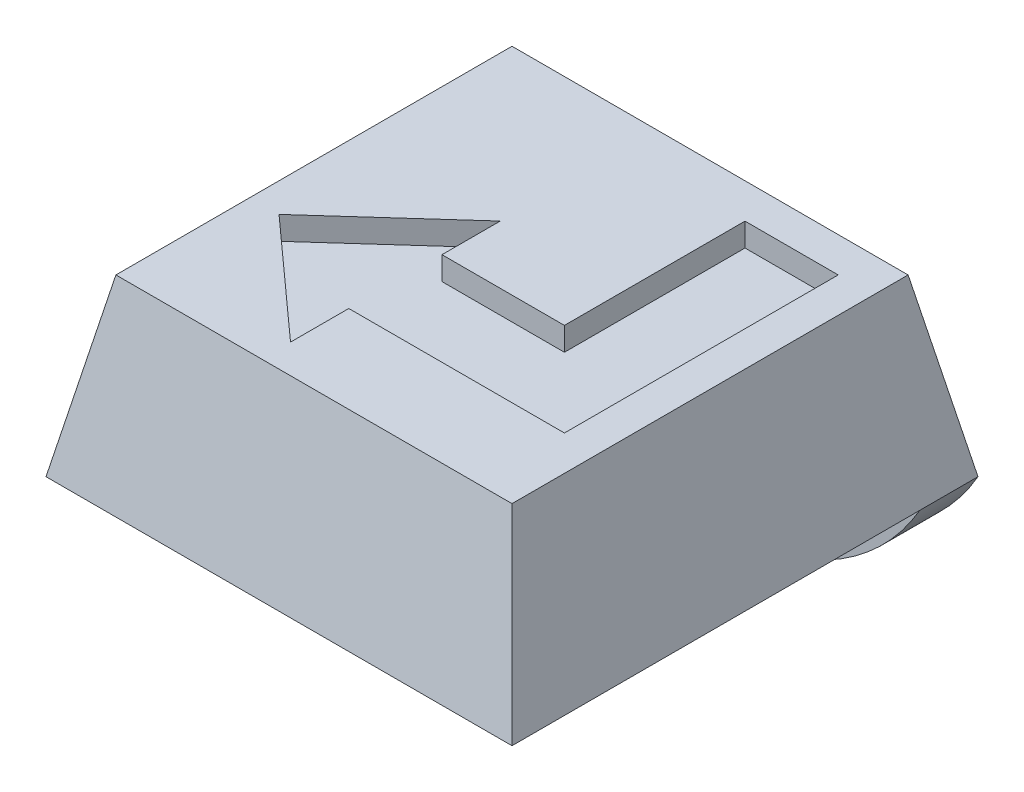
SolidWorks part; units mm, degrees
ref_plane "Front Plane" through (0, 0, 0) normal (0, 0, 1) x (1, 0, 0)
ref_plane "Top Plane" through (0, 0, 0) normal (0, 1, 0) x (1, 0, 0)
ref_plane "Right Plane" through (0, 0, 0) normal (1, 0, 0) x (0, 0, -1)
sketch "Sketch1" plane through (0, 0, 0) normal (0, 1, 0) x (1, 0, 0)
  line L1 (0, 0) -> (8, 0)
  line L2 (0, 0) -> (0, 8)
  line L3 (0, 8) -> (8, 8)
  line L4 (8, 0) -> (8, 8)
  dimension "D1" = 8
  dimension "D2" = 8
extrude "Boss-Extrude1" add sketch "Sketch1" along normal blind 3
sketch "Sketch2" plane through (0, 0, 0) normal (0, 0, 1) x (1, 0, 0)
  line L0 (0, 0) -> (0.6, 3)
  line L1 (0, 3) -> (8, 3) construction
  line L2 (0.6, 3) -> (0, 3)
  line L3 (0, 3) -> (0, 0)
  line L4 (8, 0) -> (7.4, 3)
  line L5 (7.4, 3) -> (8, 3)
  line L6 (8, 3) -> (8, 0)
  dimension "D1" = 0.6
  dimension "D2" = 0.6
extrude "Cut-Extrude1" cut sketch "Sketch2" against normal through all both and the other way through all
sketch "Sketch3" plane through (0, 0, 0) normal (1, 0, 0) x (0, 0, -1)
  line L0 (0, 0) -> (0.6, 3)
  line L1 (8, 3) -> (0, 3) construction
  line L2 (0.6, 3) -> (0, 3)
  line L3 (0, 3) -> (0, 0)
  line L4 (8, 3) -> (7.4, 3)
  line L5 (7.4, 3) -> (8, 0)
  line L6 (8, 3) -> (8, 0)
  dimension "D1" = 0.6
  dimension "D2" = 0.6
extrude "Cut-Extrude2" cut sketch "Sketch3" along normal blind 11
sketch "Sketch4" plane through (0, 0, 0) normal (0, -1, 0) x (1, 0, 0)
  line L0 (8, 0) -> (8, -8) construction
  line L3 (0, 0) -> (8, 0) construction
  circle A0 centre (4, -3.75) radius 1.75
  dimension "D1" = 3.5
  dimension "D2" = 4
  dimension "D3" = 3.75
extrude "Cut-Extrude3" cut sketch "Sketch4" against normal blind 0.4
sketch "Sketch5" plane through (0, 0, 0) normal (0, -1, 0) x (1, 0, 0)
  line L0 (8, 0) -> (8, -8) construction
  line L1 (0, -8) -> (8, -8)
  line L2 (0, -8) -> (0, -7)
  line L3 (0, -7) -> (8, -7)
  line L4 (8, -8) -> (8, -7)
  dimension "D1" = 1
extrude "Boss-Extrude2" add sketch "Sketch5" along normal blind 2
fillet "Fillet1" radius 4 2 edges at (8, -2, -7.5) (0, -2, -7.5)
sketch "Sketch6" plane through (0, 3, 0) normal (0, 1, 0) x (1, 0, 0)
  line L0 (3.0978, 3.7) -> (3.0978, 4.7)
  line L1 (5.2, 6.8) -> (6.8, 6.8)
  line L2 (5.2, 6.8) -> (5.2, 2.1)
  line L3 (5.2, 2.1) -> (6.8, 2.1)
  line L4 (6.8, 6.8) -> (6.8, 2.1)
  line L5 (5.2, 2.1) -> (3.0978, 2.1)
  line L6 (5.2, 2.1) -> (5.2, 3.7)
  line L7 (5.2, 3.7) -> (3.0978, 3.7)
  line L8 (3.0978, 2.1) -> (3.0978, 3.7)
  line L9 (3.0978, 4.7) -> (1.1, 2.9)
  line L10 (1.1, 2.9) -> (3.0978, 1.1)
  line L11 (3.0978, 1.1) -> (3.0978, 2.1)
  line L12 (7.4, 7.4) -> (7.4, 0.6) construction
  line L13 (7.4, 7.4) -> (0.6, 7.4) construction
  line L14 (7.4, 0.6) -> (0.6, 0.6) construction
  line L15 (0.6, 7.4) -> (0.6, 0.6) construction
  point P19 (3.0978, 2.9)
  dimension "D1" = 0.6
  dimension "D2" = 0.6
  dimension "D3" = 0.5
  dimension "D4" = 1
  dimension "D5" = 1
  dimension "D6" = 1.6
  dimension "D7" = 1.6
  dimension "D8" = 0.5
  dimension "D9" = 0
extrude "Cut-Extrude4" cut sketch "Sketch6" against normal blind 0.4 contours L10 L11 L8 L0 L9 | L8 L5 L2 L7 | L2 L1 L4 L3 region at (2.4319, 3, -2.9) region at (4.1489, 3, -2.9)
